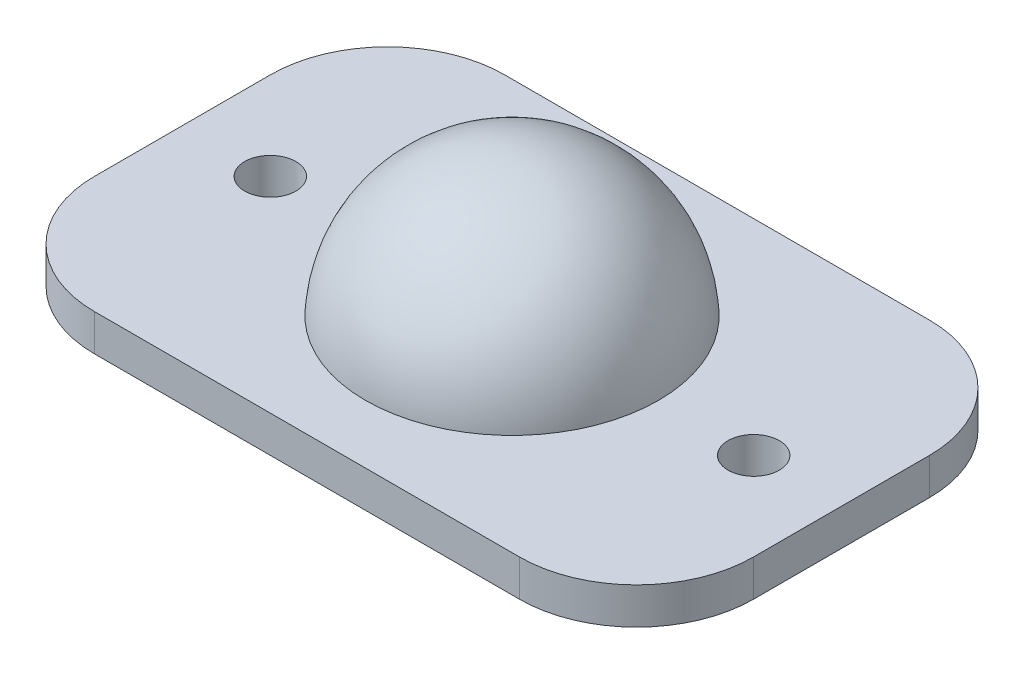
SolidWorks part; units mm, degrees
ref_plane "Front Plane" through (0, 0, 0) normal (0, 0, 1) x (1, 0, 0)
ref_plane "Top Plane" through (0, 0, 0) normal (0, 1, 0) x (1, 0, 0)
ref_plane "Right Plane" through (0, 0, 0) normal (1, 0, 0) x (0, 0, -1)
sketch "Sketch1" plane through (0, 0, 0) normal (0, 1, 0) x (1, 0, 0)
  line L1 (-14.5, -14) -> (14.5, -14)
  line L2 (-22.5, -6) -> (-22.5, 6)
  line L3 (-14.5, 14) -> (14.5, 14)
  line L4 (22.5, -6) -> (22.5, 6)
  line L5 (-22.5, -14) -> (22.5, 14) construction
  line L6 (-22.5, 14) -> (22.5, -14) construction
  arc A0 (-22.5, 6) -> (-14.5, 14) centre (-14.5, 6) cw
  arc A1 (-14.5, -14) -> (-22.5, -6) centre (-14.5, -6) cw
  arc A2 (14.5, -14) -> (22.5, -6) centre (14.5, -6) ccw
  arc A3 (14.5, 14) -> (22.5, 6) centre (14.5, 6) cw
  circle A4 centre (16.5, 0) radius 1.75
  circle A5 centre (-16.5, 0) radius 1.75
  point P0 (0, 0)
  dimension "D3" = 8
  dimension "D4" = 3.5
  dimension "D5" = 3.5
  dimension "D1" = 45
  dimension "D2" = 28
  dimension "D6" = 33
  dimension "D7" = 16.5
extrude "Boss-Extrude1" add sketch "Sketch1" along normal mid plane 2.5
sketch "Sketch2" plane through (0, 1.25, 0) normal (0, 1, 0) x (1, 0, 0)
  circle A0 centre (0, 0) radius 10
  dimension "D1" = 20
extrude "Boss-Extrude2" add sketch "Sketch2" along normal blind 9.5
fillet "Fillet1" radius 10 1 edges at (0, 10.75, 10)
